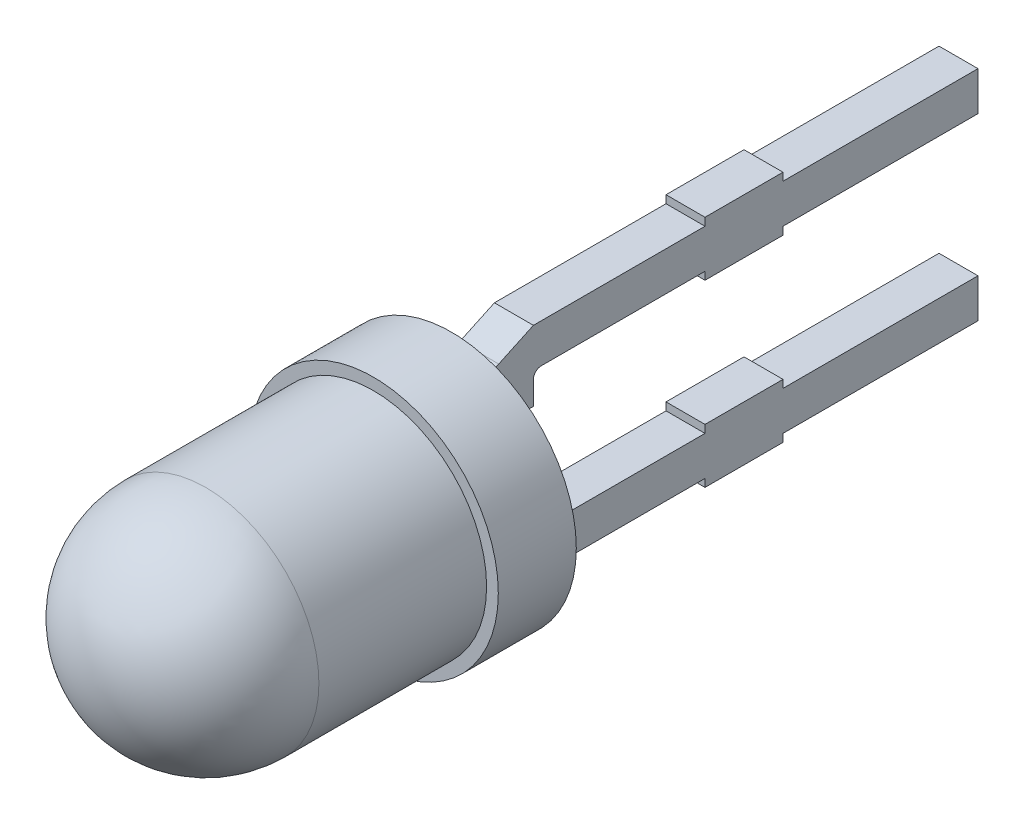
SolidWorks part; units mm, degrees
ref_plane "Front" through (0, 0, 0) normal (0, 0, 1) x (1, 0, 0)
ref_plane "Top" through (0, 0, 0) normal (0, 1, 0) x (1, 0, 0)
ref_plane "Right" through (0, 0, 0) normal (1, 0, 0) x (0, 0, -1)
sketch "Sketch1" plane through (0, 0, 0) normal (1, 0, 0) x (0, 0, -1)
  line L0 (0, 0) -> (76.2974, 0) construction
  line L1 (0, 1.45) -> (2.15, 1.45)
  line L2 (2.15, 1.45) -> (2.15, 1.6)
  line L3 (2.15, 1.6) -> (3.15, 1.6)
  line L4 (3.15, 1.6) -> (3.15, 0)
  line L5 (3.15, 0) -> (-1.45, 0)
  arc A0 (0, 1.45) -> (-1.45, 0) centre (0, 0) ccw
  dimension "D1" = 1.45
  dimension "D2" = 4.6
  dimension "D3" = 1
  dimension "D4" = 1.6
revolve "Revolve1" add sketch "Sketch1" angle 360 about L0
sketch "Sketch2" plane through (0, 0, 0) normal (1, 0, 0) x (0, 0, -1)
  line L0 (3.15, -1.6) -> (3.15, 1.6) construction
  line L1 (3.15, -1.6) -> (3.15, 1.6) construction
  line L2 (3.15, 1.027) -> (3.95, 1.4)
  line L3 (3.95, 1.4) -> (6.15, 1.4)
  line L4 (6.15, 1.4) -> (6.15, 1.5)
  line L5 (6.15, 1.5) -> (7.15, 1.5)
  line L6 (7.15, 1.5) -> (7.15, 1.4)
  line L7 (7.15, 1.4) -> (30.15, 1.4)
  line L8 (30.15, 1.4) -> (30.15, 0.9)
  line L9 (30.15, 0.9) -> (7.15, 0.9)
  line L10 (7.15, 0.9) -> (7.15, 0.8)
  line L11 (7.15, 0.8) -> (6.15, 0.8)
  line L12 (6.15, 0.8) -> (6.15, 0.9)
  line L13 (6.15, 0.9) -> (4.05, 0.9)
  line L14 (3.95, 0.8) -> (3.95, 0.5)
  line L15 (3.95, 0.5) -> (3.15, 0.5)
  line L16 (3.15, 0) -> (7.9733, 0) construction
  line L17 (3.15, 1.027) -> (3.15, 0.5)
  line L18 (3.95, -0.8) -> (3.95, -0.5)
  line L19 (6.15, -0.9) -> (4.05, -0.9)
  line L20 (6.15, -0.8) -> (6.15, -0.9)
  line L21 (7.15, -0.8) -> (6.15, -0.8)
  line L22 (7.15, -0.9) -> (7.15, -0.8)
  line L23 (30.15, -0.9) -> (7.15, -0.9)
  line L24 (30.15, -1.4) -> (30.15, -0.9)
  line L25 (7.15, -1.4) -> (30.15, -1.4)
  line L26 (7.15, -1.5) -> (7.15, -1.4)
  line L27 (6.15, -1.5) -> (7.15, -1.5)
  line L28 (6.15, -1.4) -> (6.15, -1.5)
  line L29 (3.95, -1.4) -> (6.15, -1.4)
  line L30 (3.15, -1.027) -> (3.95, -1.4)
  line L31 (3.15, -1.027) -> (3.15, -0.5)
  line L32 (3.95, -0.5) -> (3.15, -0.5)
  arc A0 (4.05, 0.9) -> (3.95, 0.8) centre (4.05, 0.8) ccw
  arc A1 (4.05, -0.9) -> (3.95, -0.8) centre (4.05, -0.8) cw
  point P19 (3.15, 0)
  dimension "D1" = 0.5
  dimension "D2" = 0.7
  dimension "D3" = 1.4
  dimension "D4" = 0.8
  dimension "D5" = 27
  dimension "D6" = 115
  dimension "D7" = 4
  dimension "D8" = 1
  dimension "D9" = 0.5
  dimension "D10" = 0.1
extrude "Extrude1" add sketch "Sketch2" along normal mid plane 0.5
fillet "Fillet1" radius 0.25 8 edges at (0, -0.5, -3.15) (0, -1.027, -3.15) (-0.25, -0.7635, -3.15) (0, 0.5, -3.15) (-0.25, 0.7635, -3.15) (0, 1.027, -3.15) (0.25, 0.7635, -3.15) (0.25, -0.7635, -3.15)
sketch "Sketch3" plane through (0, 0, 0) normal (1, 0, 0) x (0, 0, -1)
  line L0 (7.15, -1.4) -> (30.15, -1.4) construction
  line L1 (30.15, 1.4) -> (18.15, 1.4)
  line L2 (30.15, 1.4) -> (30.15, -1.4)
  line L3 (30.15, -1.4) -> (18.15, -1.4)
  line L4 (18.15, 1.4) -> (18.15, -1.4)
  line L5 (3.15, -1.6) -> (3.15, 1.6) construction
  dimension "D1" = 15
extrude "Cut-Extrude1" cut sketch "Sketch3" against normal through all both and the other way through all
sketch "Sketch4" plane through (0, 0, 0) normal (1, 0, 0) x (0, 0, -1)
  line L0 (3.15, -1.6) -> (3.15, 1.6) construction
  line L1 (9.65, 2.5679) -> (20.176, 2.5679)
  line L2 (9.65, 2.5679) -> (9.65, -2.4323)
  line L3 (9.65, -2.4323) -> (20.176, -2.4323)
  line L4 (20.176, 2.5679) -> (20.176, -2.4323)
  dimension "D1" = 6.5
extrude "Cut-Extrude2" cut sketch "Sketch4" against normal through all both and the other way through all
